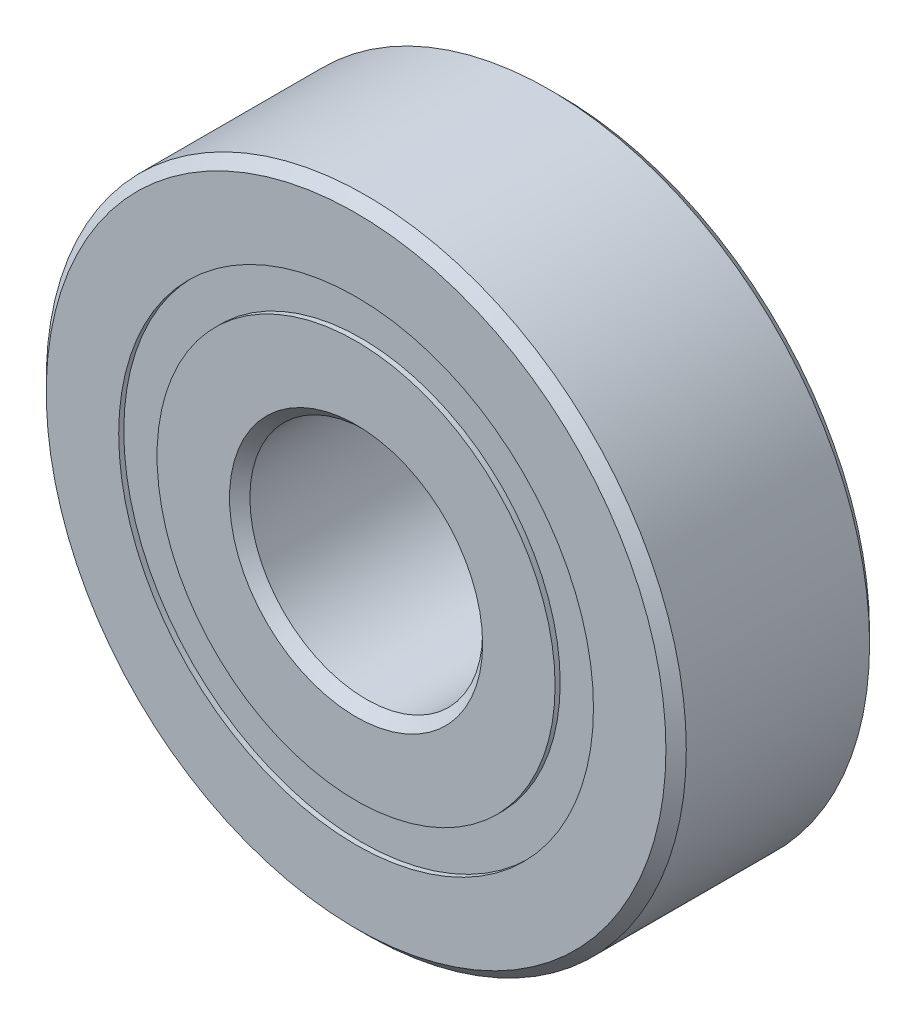
SolidWorks part; units mm, degrees
ref_plane "Front Plane" through (0, 0, 0) normal (0, 0, 1) x (1, 0, 0)
ref_plane "Top Plane" through (0, 0, 0) normal (0, 1, 0) x (1, 0, 0)
ref_plane "Right Plane" through (0, 0, 0) normal (1, 0, 0) x (0, 0, -1)
sketch "Sketch1" plane through (0, 0, 0) normal (1, 0, 0) x (0, 0, -1)
  line L0 (-3.5, 0) -> (3.5, 0) construction
  line L1 (0, 11) -> (0, -11) construction
  line L2 (3.15, 11) -> (-3.15, 11)
  line L3 (-3.15, 11) -> (-3.5, 10.65)
  line L4 (-3.5, 10.65) -> (-3.5, 8.1593)
  line L5 (-3.5, 8.1593) -> (-1.5556, 8.1593)
  line L6 (3.5, 8.1593) -> (1.5556, 8.1593)
  line L7 (3.5, 10.65) -> (3.5, 8.1593)
  line L8 (3.15, 11) -> (3.5, 10.65)
  line L9 (0, 11) -> (0, 7.5) construction
  line L10 (0, 7.5) -> (0, 4) construction
  arc A0 (-1.5556, 8.1593) -> (1.5556, 8.1593) centre (0, 7.5) cw
  point P14 (0, 4)
  dimension "Width" = 7
  dimension "OD" = 22
  dimension "D1" = 45
  dimension "D2" = 0.35
  dimension "Shaft Dia" = 8
  dimension "D3" = 3.1111
  dimension "D4" = 0.6593
revolve "Revolve1" add sketch "Sketch1" angle 360 about L0
sketch "Sketch3" plane through (0, 0, 0) normal (1, 0, 0) x (0, 0, -1)
  line L0 (-3.5, 6.8407) -> (-1.5556, 6.8407)
  line L1 (0, 11) -> (0, -11) construction
  line L2 (-3.5, 10.65) -> (-3.5, 8.1593) construction
  line L3 (-3.5, 6.8407) -> (-3.5, 4.35)
  line L4 (-3.15, 11) -> (-3.5, 10.65) construction
  line L5 (-3.5, 4.35) -> (-3.15, 4)
  line L6 (-3.15, 4) -> (3.15, 4)
  line L7 (3.15, 11) -> (3.15, -11) construction
  line L8 (3.15, 4) -> (3.5, 4.35)
  line L9 (3.5, -10.65) -> (3.5, 10.65) construction
  line L10 (3.5, 4.35) -> (3.5, 6.8407)
  line L11 (3.5, 6.8407) -> (1.5556, 6.8407)
  line L13 (3.15, 11) -> (3.5, 10.65) construction
  arc A0 (1.5556, 8.1593) -> (-1.5556, 8.1593) centre (0, 7.5) ccw construction
  arc A1 (1.5556, 6.8407) -> (-1.5556, 6.8407) centre (0, 7.5) cw
revolve "Revolve3" add sketch "Sketch3" angle 360 about L0
sketch "Sketch4" plane through (0, 0, 0) normal (1, 0, 0) x (0, 0, -1)
  line L0 (-1.6895, 7.5) -> (1.6895, 7.5)
  arc A2 (-1.6895, 7.5) -> (1.6895, 7.5) centre (0, 7.5) cw
  arc A3 (1.5556, 8.1593) -> (-1.5556, 8.1593) centre (0, 7.5) ccw construction
revolve "Revolve4" add sketch "Sketch4" angle 360 about L0
ref_axis "Axis1" through (0, 0, -3.5) along (0, 0, 1)
pattern_circular "CirPattern1" count 12 every 30 about axis through (0, 0, -3.5) along (0, 0, 1) of bodies 104
sketch "Sketch5" plane through (0, 0, 0) normal (1, 0, 0) x (0, 0, -1)
  line L0 (-3.5, 8.1593) -> (-1.5556, 8.1593) construction
  line L1 (-3.325, 8.1593) -> (-1.6895, 8.1593)
  line L2 (-3.325, 8.1593) -> (-3.325, 6.8407)
  line L3 (-3.325, 6.8407) -> (-1.6895, 6.8407)
  line L4 (-1.6895, 8.1593) -> (-1.6895, 6.8407)
  line L5 (-3.5, 6.8407) -> (-1.5556, 6.8407) construction
  line L6 (3.5, 8.1593) -> (1.5556, 8.1593) construction
  line L7 (3.325, 8.1593) -> (1.6895, 8.1593)
  line L8 (3.325, 8.1593) -> (3.325, 6.8407)
  line L9 (3.325, 6.8407) -> (1.6895, 6.8407)
  line L10 (1.6895, 8.1593) -> (1.6895, 6.8407)
  line L11 (3.5, 6.8407) -> (1.5556, 6.8407) construction
  line L12 (-3.15, 11) -> (-3.5, 10.65) construction
  point P18 (-3.325, 10.825)
revolve "Revolve5" add sketch "Sketch5" angle 360 about L0
equation "\"D2@Sketch1\" = \"Width@Sketch1\"*.05"
equation "\"D3@Sketch1\" = \"Width@Sketch1\"/2.25"
equation "\"D4@Sketch1\" = (((\"OD@Sketch1\"-\"Width@Sketch1\")/2)/3.25)/3.5"
equation "\"D2@CirPattern1\" = 360/\"Balls@CirPattern1\""
